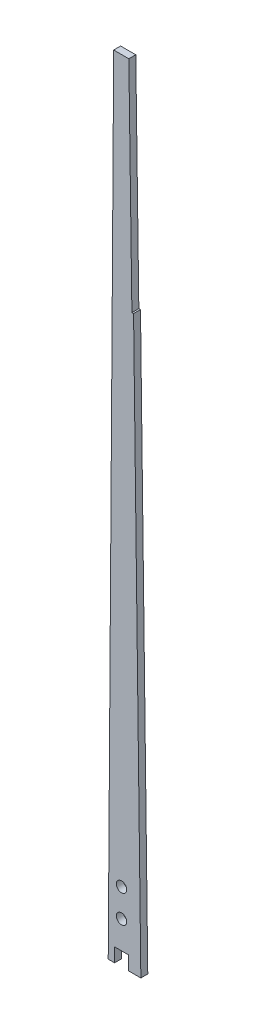
SolidWorks part; units mm, degrees
ref_plane "XY" through (0, 0, 0) normal (0, 0, 1) x (1, 0, 0)
ref_plane "XZ" through (0, 0, 0) normal (0, 1, 0) x (1, 0, 0)
ref_plane "YZ" through (0, 0, 0) normal (1, 0, 0) x (0, 0, -1)
ref_axis "X" through (-34.925, 0, 0) along (1, 0, 0)
ref_axis "Y" through (0, -53.3373, 0) along (0, 1, 0)
ref_axis "Z" through (0, 0, 3.3337) along (0, 0, -1)
sketch "Sketch3" plane through (0, 0, 0) normal (0, 0, 1) x (1, 0, 0)
  line B0 (6.1442, 399.996) -> (-1.5646, 399.996)
  arc B1 (10.9787, 29.7914) -> (-4.1092, 31.483) centre (0, 0) ccw
  spline B2 degree 3 poles (-2.2314, 299.996) (-2.2349, 299.49) (-2.393, 276.4245) (-2.5531, 253.359) (-2.8683, 208.24) (-3.0269, 185.6805) (-3.3464, 140.3) (-3.6556, 96.4207) (-3.9627, 52.5413) (-4.1092, 31.483) knots 0 0 0 0 0.005653 0.257702 0.257702 0.509751 0.509751 0.764723 1 1 1 1
  spline B3 degree 3 poles (-1.5646, 399.996) (-1.6372, 388.7162) (-1.7108, 377.4364) (-1.931, 344.1246) (-2.0802, 322.0711) (-2.2313, 300.0175) (-2.2314, 299.996) knots 0 0 0 0 0.338393 0.338393 0.999354 1 1 1 1
  spline B4 degree 3 poles (7.5462, 299.996) (7.092, 333.3295) (6.6238, 366.6628) (6.1442, 399.996) knots 0 0 0 0 1 1 1 1
  spline B5 degree 3 poles (10.9787, 29.7914) (9.9109, 119.8606) (8.7733, 209.9289) (7.5462, 299.996) knots 0 0 0 0 1 1 1 1
sketch_block_instance "Block-RearSpar-1"
sketch_block "Block-RearSpar"
sketch "Sketch4" plane through (0, 0, 0) normal (0, 0, 1) x (1, 0, 0)
  line L2 (6.1442, 399.996) -> (-1.5646, 399.996) construction
  line L3 (6.1442, 399.996) -> (-1.5646, 399.996)
  arc A0 (10.9787, 29.7914) -> (-4.1092, 31.483) centre (0, 0) ccw construction
  arc A1 (10.9787, 29.7914) -> (-4.1092, 31.483) centre (0, 0) ccw
  spline S2 degree 3 poles (-121.6535, 2293.9975) (5.1575, 1627.3849) (2.2169, 940.3657) (-2.5531, 253.359) (-2.8683, 208.24) (-3.0269, 185.6805) (-3.3464, 140.3) (-8.3535, -570.1873) (-12.8071, -1280.6785) (-1.472, -1968.4561) knots -7.417974 -7.417974 -7.417974 -7.417974 0.005653 0.257702 0.257702 0.509751 0.509751 0.764723 8.447775 8.447775 8.447775 8.447775 only from (-2.2314, 299.996) to (-4.1092, 31.483) construction
  spline S3 degree 3 poles (-46.2092, 2399.0845) (3.9416, 1721.255) (2.6931, 1043.695) (-1.931, 344.1246) (-5.1261, -128.2574) (-9.209, -600.6333) (-435.2561, -1640.5057) knots -19.987749 -19.987749 -19.987749 -19.987749 0.338393 0.338393 0.999354 14.509863 14.509863 14.509863 14.509863 only from (-1.5646, 399.996) to (-2.2314, 299.996) construction
  spline S4 degree 3 poles (-2.9312, -1699.8175) (44.279, -332.5444) (-19.8869, 1033.1673) (-15.4341, 2399.841) knots -19.992737 -19.992737 -19.992737 -19.992737 20.997545 20.997545 20.997545 20.997545 only from (7.5462, 299.996) to (6.1442, 399.996) construction
  spline S5 degree 3 poles (31.3042, -1970.0909) (13.5099, -546.9668) (15.0768, 876.6883) (-42.477, 2299.3052) knots -7.401386 -7.401386 -7.401386 -7.401386 8.400667 8.400667 8.400667 8.400667 only from (10.9787, 29.7914) to (7.5462, 299.996) construction
  spline S6 degree 3 poles (-2.2314, 299.996) (-2.2349, 299.49) (-2.393, 276.4245) (-2.5531, 253.359) (-2.8683, 208.24) (-3.0269, 185.6805) (-3.3464, 140.3) (-3.6556, 96.4207) (-3.9627, 52.5413) (-4.1092, 31.483) knots 0 0 0 0 0.005653 0.257702 0.257702 0.509751 0.509751 0.764723 1 1 1 1
  spline S7 degree 3 poles (-1.5646, 399.996) (-1.6372, 388.7162) (-1.7108, 377.4364) (-1.931, 344.1246) (-2.0802, 322.0711) (-2.2313, 300.0175) (-2.2314, 299.996) knots 0 0 0 0 0.338393 0.338393 0.999354 1 1 1 1
  spline S8 degree 3 poles (7.5462, 299.996) (7.092, 333.3295) (6.6238, 366.6628) (6.1442, 399.996) knots 0 0 0 0 1 1 1 1
  spline S9 degree 3 poles (10.9787, 29.7914) (9.9109, 119.8606) (8.7733, 209.9289) (7.5462, 299.996) knots 0 0 0 0 1 1 1 1
extrude "Boss-Extrude2" add sketch "Sketch4" along normal blind 3.175
sketch "Sketch5" plane through (0, 0, 0) normal (0, 0, 1) x (1, 0, 0)
  line L0 (0, 0) -> (2.032, 44.45) construction
  line L1 (-7.828, 0) -> (14.6509, 0)
  line L2 (-7.828, 0) -> (-7.828, 38.1)
  line L4 (14.6509, 0) -> (14.6509, 38.1)
  line L5 (-1.143, 38.1) -> (-1.143, 44.45)
  line L6 (-1.143, 44.45) -> (5.207, 44.45)
  line L7 (5.207, 38.1) -> (5.207, 44.45)
  line L8 (2.032, 44.45) -> (2.032, 38.1) construction
  line L10 (5.207, 38.1) -> (-1.143, 38.1) construction
  line L12 (14.6509, 38.1) -> (5.207, 38.1)
  line L13 (-1.143, 38.1) -> (-7.828, 38.1)
  circle A1 centre (0, 0) radius 31.75 construction
  point P0 (2.032, 44.45)
  dimension "D1" = 2.032
  dimension "D2" = 38.1
  dimension "D3" = 6.35
  dimension "D4" = 6.35
extrude "Cut-Extrude1" cut sketch "Sketch5" along normal through all
sketch "Sketch6" plane through (0, 0, 3.175) normal (0, 0, 1) x (1, 0, 0)
  line L0 (6.1442, 399.996) -> (7.546, 300.0058)
  line L1 (6.1442, 399.996) -> (5.3822, 399.996)
  line L2 (7.546, 300.0058) -> (6.7842, 299.9951)
  line L3 (5.3822, 399.996) -> (6.7842, 299.9951)
  line L4 (6.1442, 399.996) -> (-1.5646, 399.996) construction
  spline S0 degree 3 poles (7.5462, 299.996) (7.092, 333.3295) (6.6238, 366.6628) (6.1442, 399.996) knots 0 0 0 0 1 1 1 1 construction
  point P7 (5.3822, 399.996)
  dimension "D1" = 100
  dimension "D2" = 0.762
extrude "Cut-Extrude2" cut sketch "Sketch6" against normal through all body kept at (5.3822, 399.996, 0)
hole_wizard "3/16 (0.1875) Dowel Hole1" positions "Sketch7" profile "Sketch8" hole size "3/16" standard "ANSI Inch"
sketch "Sketch7" plane through (0, 0, 3.175) normal (0, 0, 1) x (1, 0, 0)
  line L0 (2.032, 69.85) -> (2.032, 57.15) construction
  line L1 (2.032, 57.15) -> (2.032, 44.45) construction
  line L2 (5.207, 44.45) -> (-1.143, 44.45) construction
  point P0 (2.032, 57.15)
  point P2 (2.032, 69.85)
  dimension "D1" = 12.7
  dimension "D2" = 12.7
sketch "Sketch8" plane through (2.032, 57.15, 3.175) normal (1, 0, 0) x (0, -1, 0)
  line L0 (0, 0) -> (0, 12.0988)
  line L1 (0, 12.0988) -> (2.3812, 10.668)
  line L2 (2.3812, 10.668) -> (2.3812, 0)
  line L5 (2.3812, 0) -> (0, 0)
  line L10 (0, 12.0988) -> (-2.3812, 10.668) construction
  line L11 (0, -6.35) -> (0, 107.95) construction
  dimension "Hole Dia." = 4.7625
  dimension "Hole Depth" = 10.668
  dimension "Drill Angle" = 118
